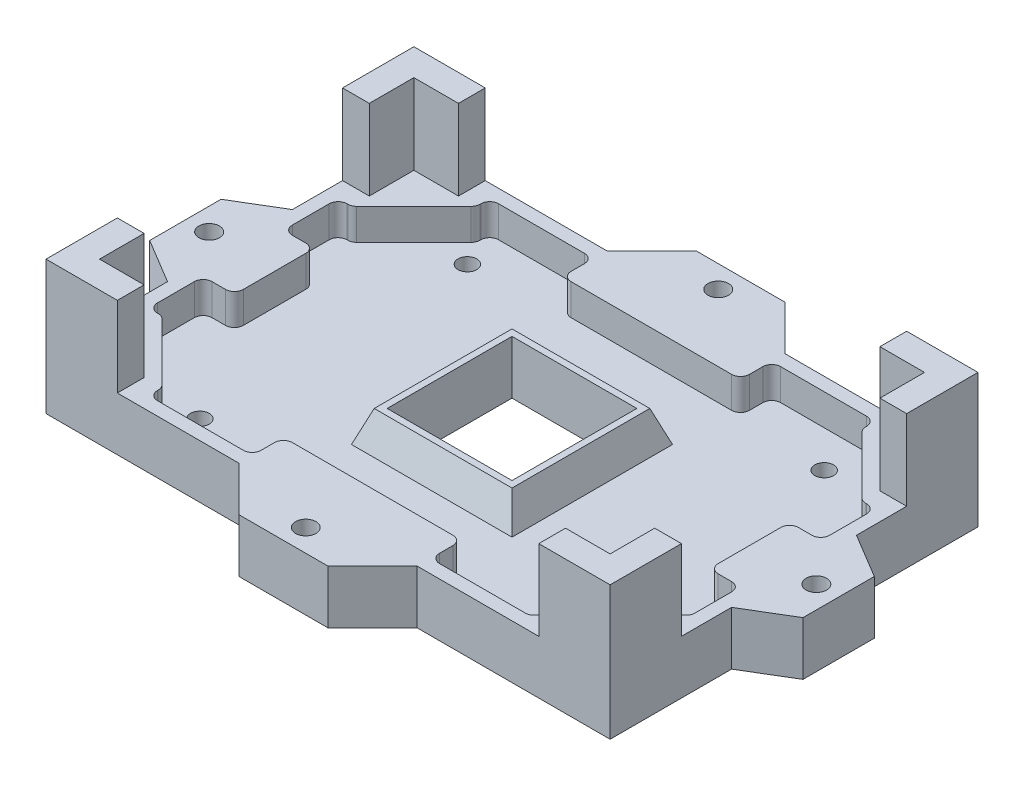
SolidWorks part; units mm, degrees
ref_plane "Спереди" through (0, 0, 0) normal (0, 0, 1) x (1, 0, 0)
ref_plane "Сверху" through (0, 0, 0) normal (0, 1, 0) x (1, 0, 0)
ref_plane "Справа" through (0, 0, 0) normal (1, 0, 0) x (0, 0, -1)
ref_plane "Плоскость4" through (0, 77.196, 0) normal (0, 1, 0) x (1, 0, 0)
sketch "Эскиз1" plane through (0, 77.196, 0) normal (0, 1, 0) x (1, 0, 0)
  line L0 (50.809, -75.5231) -> (50.809, -103.5231)
  line L1 (50.809, -103.5231) -> (78.809, -103.5231)
  line L2 (78.809, -103.5231) -> (78.809, -75.5231)
  line L3 (78.809, -75.5231) -> (50.809, -75.5231)
  line L4 (1.559, -48.2731) -> (1.559, -130.7731)
  line L5 (1.559, -130.7731) -> (128.059, -130.7731)
  line L6 (128.059, -130.7731) -> (128.059, -48.2731)
  line L7 (128.059, -48.2731) -> (1.559, -48.2731)
  circle A0 centre (24.809, -59.5231) radius 2.1
  circle A1 centre (104.809, -59.5231) radius 2.1
  circle A2 centre (104.809, -119.5231) radius 2.1
  circle A3 centre (24.809, -119.5231) radius 2.1
extrude "Бобышка-Вытянуть1" add sketch "Эскиз1" along normal blind 5
ref_plane "Плоскость5" through (0, 82.196, 0) normal (0, 1, 0) x (1, 0, 0)
sketch "Эскиз2" plane through (0, 82.196, 0) normal (0, 1, 0) x (1, 0, 0)
  line L0 (46.809, -71.5231) -> (82.809, -71.5231)
  line L1 (46.809, -107.5231) -> (82.809, -107.5231)
  line L2 (78.809, -103.5231) -> (78.809, -75.5231)
  line L3 (78.809, -75.5231) -> (50.809, -75.5231)
  line L4 (82.809, -107.5231) -> (82.809, -71.5231)
  line L5 (46.809, -71.5231) -> (46.809, -107.5231)
  line L6 (50.809, -75.5231) -> (50.809, -103.5231) construction
  line L7 (78.809, -75.5231) -> (50.809, -75.5231) construction
  line L8 (50.809, -75.5231) -> (50.809, -103.5231)
  line L9 (50.809, -103.5231) -> (78.809, -103.5231)
  line L14 (1.559, -48.2731) -> (1.559, -68.2731)
  line L15 (1.559, -48.2731) -> (1.559, -130.7731) construction
  line L16 (1.559, -48.2731) -> (21.559, -48.2731)
  line L17 (128.059, -48.2731) -> (1.559, -48.2731) construction
  line L18 (21.559, -48.2731) -> (21.559, -54.2731)
  line L19 (1.559, -68.2731) -> (7.559, -68.2731)
  line L20 (7.559, -68.2731) -> (21.559, -54.2731)
  line L21 (1.559, -130.7731) -> (21.559, -130.7731)
  line L22 (1.559, -130.7731) -> (128.059, -130.7731) construction
  line L23 (21.559, -130.7731) -> (21.559, -124.7731)
  line L24 (1.559, -130.7731) -> (1.559, -110.7731)
  line L25 (1.559, -110.7731) -> (7.559, -110.7731)
  line L26 (7.559, -110.7731) -> (21.559, -124.7731)
  line L27 (128.059, -48.2731) -> (108.059, -48.2731)
  line L28 (128.059, -48.2731) -> (128.059, -68.2731)
  line L29 (128.059, -130.7731) -> (128.059, -48.2731) construction
  line L30 (108.059, -48.2731) -> (108.059, -54.2731)
  line L31 (128.059, -68.2731) -> (122.059, -68.2731)
  line L32 (122.059, -68.2731) -> (108.059, -54.2731)
  line L33 (128.059, -130.7731) -> (108.059, -130.7731)
  line L34 (-8.25, -130.7731) -> (8.25, -130.7731) construction
  line L35 (128.059, -130.7731) -> (128.059, -110.7731)
  line L36 (128.059, -110.7731) -> (122.059, -110.7731)
  line L37 (108.059, -130.7731) -> (108.059, -124.7731)
  line L38 (108.059, -124.7731) -> (122.059, -110.7731)
  line L39 (118.059, -80.5231) -> (128.059, -80.5231)
  line L40 (128.059, -80.5231) -> (128.059, -98.5231)
  line L41 (128.059, -98.5231) -> (118.059, -98.5231)
  line L42 (118.059, -98.5231) -> (118.059, -80.5231)
  line L45 (44.809, -48.2731) -> (44.809, -58.2731)
  line L46 (44.809, -58.2731) -> (84.809, -58.2731)
  line L47 (84.809, -58.2731) -> (84.809, -48.2731)
  line L48 (44.809, -48.2731) -> (84.809, -48.2731)
  line L49 (1.559, -80.5231) -> (1.559, -98.5231)
  line L50 (1.559, -98.5231) -> (11.559, -98.5231)
  line L51 (11.559, -98.5231) -> (11.559, -80.5231)
  line L52 (11.559, -80.5231) -> (1.559, -80.5231)
  line L53 (44.809, -130.7731) -> (84.809, -130.7731)
  line L54 (84.809, -130.7731) -> (84.809, -120.7731)
  line L55 (84.809, -120.7731) -> (44.809, -120.7731)
  line L56 (44.809, -130.7731) -> (44.809, -120.7731)
  line L57 (21.559, -48.2731) -> (21.559, -51.2731)
  line L58 (21.559, -51.2731) -> (44.809, -51.2731)
  line L59 (44.809, -51.2731) -> (44.809, -48.2731)
  line L60 (44.809, -48.2731) -> (21.559, -48.2731)
  line L61 (108.059, -48.2731) -> (108.059, -51.2731)
  line L62 (108.059, -51.2731) -> (84.809, -51.2731)
  line L63 (84.809, -51.2731) -> (84.809, -48.2731)
  line L64 (128.059, -68.2731) -> (125.059, -68.2731)
  line L65 (125.059, -68.2731) -> (125.059, -80.5231)
  line L66 (125.059, -80.5231) -> (128.059, -80.5231)
  line L67 (128.059, -80.5231) -> (128.059, -68.2731)
  line L68 (128.059, -110.7731) -> (125.059, -110.7731)
  line L69 (125.059, -110.7731) -> (125.059, -98.5231)
  line L70 (125.059, -98.5231) -> (128.059, -98.5231)
  line L71 (128.059, -110.7731) -> (128.059, -98.5231)
  line L72 (108.059, -130.7731) -> (108.059, -127.7731)
  line L73 (108.059, -127.7731) -> (84.809, -127.7731)
  line L74 (84.809, -127.7731) -> (84.809, -130.7731)
  line L75 (108.059, -130.7731) -> (84.809, -130.7731)
  line L76 (21.559, -130.7731) -> (21.559, -127.7731)
  line L77 (21.559, -127.7731) -> (44.809, -127.7731)
  line L78 (44.809, -127.7731) -> (44.809, -130.7731)
  line L79 (44.809, -130.7731) -> (21.559, -130.7731)
  line L80 (21.559, -130.7731) -> (21.559, -127.7731)
  line L81 (1.559, -68.2731) -> (4.559, -68.2731)
  line L82 (4.559, -68.2731) -> (4.559, -80.5231)
  line L83 (4.559, -80.5231) -> (1.559, -80.5231)
  line L84 (1.559, -68.2731) -> (1.559, -80.5231)
  line L85 (1.559, -110.7731) -> (4.559, -110.7731)
  line L86 (4.559, -110.7731) -> (4.559, -98.5231)
  line L87 (4.559, -98.5231) -> (1.559, -98.5231)
  line L88 (1.559, -98.5231) -> (1.559, -110.7731)
  line L89 (84.809, -48.2731) -> (108.059, -48.2731)
  line L90 (128.059, -80.5231) -> (128.059, -68.2731)
  line L91 (128.059, -110.7731) -> (128.059, -98.5231)
extrude "Бобышка-Вытянуть2" add sketch "Эскиз2" along normal blind 7 contours L19 L20 L18 L16 L14 | L45 L60 L18 L58 | L48 L45 L46 L47 | L89 L47 L62 L30 | L32 L31 L28 L27 L30 | L39 L67 L31 L65 | L42 L41 L40 L39 | L36 L71 L41 L69 | L38 L37 L33 L35 L36 | L75 L37 L73 L54 | L0 L5 L1 L4 L9 L8 L3 L2 | L56 L53 L54 L55 | L79 L56 L77 L23 | L26 L25 L24 L21 L23 | L50 L88 L25 L86 | L51 L52 L49 L50 | L19 L84 L52 L82 region at (64.809, 82.196, 72.0322) region at (9.8283, 82.196, 56.5424) region at (3.059, 82.196, 74.3981) region at (33.184, 82.196, 49.7731) region at (6.559, 82.196, 89.5231) region at (64.809, 82.196, 53.2731) region at (3.059, 82.196, 104.6481) region at (96.434, 82.196, 49.7731) region at (9.8283, 82.196, 122.5038) region at (119.7897, 82.196, 56.5424) region at (33.184, 82.196, 129.2731) region at (126.559, 82.196, 74.3981) region at (64.809, 82.196, 125.7731) region at (123.059, 82.196, 89.5231) region at (96.434, 82.196, 129.2731) region at (126.559, 82.196, 104.6481) region at (119.7897, 82.196, 122.5038)
chamfer "Фаска1" distance 7 angle 20 4 edges at (82.809, 89.196, 89.5231) (64.809, 89.196, 71.5231) (46.809, 89.196, 89.5231) (64.809, 89.196, 107.5231) first distance on face at (82.809, 85.696, 89.5231) first distance on face at (64.809, 85.696, 71.5231) first distance on face at (46.809, 85.696, 89.5231) first distance on face at (64.809, 85.696, 107.5231)
fillet "Скругление1" radius 2 32 edges at (44.809, 85.696, 120.7731) (44.809, 85.696, 127.7731) (21.559, 85.696, 124.7731) (21.559, 85.696, 127.7731) (7.559, 85.696, 110.7731) (4.559, 85.696, 110.7731) (11.559, 85.696, 98.5231) (4.559, 85.696, 98.5231) (11.559, 85.696, 80.5231) (4.559, 85.696, 80.5231) (4.559, 85.696, 68.2731) (84.809, 85.696, 120.7731) (84.809, 85.696, 127.7731) (108.059, 85.696, 127.7731) (108.059, 85.696, 124.7731) (122.059, 85.696, 110.7731) (125.059, 85.696, 110.7731) (125.059, 85.696, 98.5231) (118.059, 85.696, 98.5231) (118.059, 85.696, 80.5231) (125.059, 85.696, 80.5231) (125.059, 85.696, 68.2731) (122.059, 85.696, 68.2731) (108.059, 85.696, 54.2731) (108.059, 85.696, 51.2731) (84.809, 85.696, 51.2731) (84.809, 85.696, 58.2731) (44.809, 85.696, 51.2731) (21.559, 85.696, 51.2731) (44.809, 85.696, 58.2731) (7.559, 85.696, 68.2731) (21.559, 85.696, 54.2731)
ref_plane "Плоскость6" through (0, 89.196, 0) normal (0, 1, 0) x (1, 0, 0)
sketch "Эскиз3" plane through (0, 89.196, 0) normal (0, 1, 0) x (1, 0, 0)
  line L0 (1.559, -48.2731) -> (1.559, -64.2731)
  line L1 (1.559, -48.2731) -> (1.559, -130.7731) construction
  line L2 (1.559, -64.2731) -> (7.559, -64.2731)
  line L3 (1.559, -48.2731) -> (17.559, -48.2731)
  line L4 (1.559, -48.2731) -> (128.059, -48.2731) construction
  line L5 (17.559, -48.2731) -> (17.559, -54.2731)
  line L6 (17.559, -54.2731) -> (7.559, -54.2731)
  line L7 (7.559, -54.2731) -> (7.559, -64.2731)
  line L8 (1.559, -130.7731) -> (1.559, -114.7731)
  line L9 (-8.25, -130.7731) -> (8.25, -130.7731) construction
  line L10 (1.559, -114.7731) -> (7.559, -114.7731)
  line L11 (1.559, -130.7731) -> (17.559, -130.7731)
  line L12 (17.559, -130.7731) -> (17.559, -124.7731)
  line L13 (17.559, -124.7731) -> (7.559, -124.7731)
  line L14 (7.559, -124.7731) -> (7.559, -114.7731)
  line L15 (128.059, -48.2731) -> (128.059, -64.2731)
  line L16 (128.059, -48.2731) -> (128.059, -130.7731) construction
  line L17 (128.059, -64.2731) -> (122.059, -64.2731)
  line L18 (128.059, -48.2731) -> (112.059, -48.2731)
  line L19 (112.059, -48.2731) -> (112.059, -54.2731)
  line L20 (112.059, -54.2731) -> (122.059, -54.2731)
  line L21 (122.059, -54.2731) -> (122.059, -64.2731)
  line L22 (128.059, -130.7731) -> (128.059, -114.7731)
  line L23 (128.059, -114.7731) -> (122.059, -114.7731)
  line L24 (128.059, -130.7731) -> (112.059, -130.7731)
  line L26 (112.059, -130.7731) -> (112.059, -124.7731)
  line L27 (112.059, -124.7731) -> (122.059, -124.7731)
  line L28 (122.059, -124.7731) -> (122.059, -114.7731)
extrude "Бобышка-Вытянуть3" add sketch "Эскиз3" along normal blind 18
sketch "Эскиз4" plane through (0, 89.196, 0) normal (0, 1, 0) x (1, 0, 0)
  line L0 (-8.441, -81.5231) -> (-8.441, -97.5231)
  line L1 (1.559, -64.2731) -> (1.559, -114.7731) construction
  line L2 (1.559, -81.5231) -> (1.559, -75.5231)
  line L3 (-8.441, -81.5231) -> (1.559, -81.5231)
  line L4 (1.559, -81.5231) -> (1.559, -97.5231)
  line L5 (1.559, -97.5231) -> (-8.441, -97.5231)
  line L6 (1.559, -75.5231) -> (-8.441, -81.5231)
  line L7 (1.559, -97.5231) -> (1.559, -103.5231)
  line L8 (1.559, -103.5231) -> (-8.441, -97.5231)
  line L9 (128.059, -81.5231) -> (128.059, -97.5231)
  line L10 (128.059, -64.2731) -> (128.059, -114.7731) construction
  line L11 (128.059, -97.5231) -> (138.059, -97.5231)
  line L12 (138.059, -97.5231) -> (138.059, -81.5231)
  line L13 (138.059, -81.5231) -> (128.059, -81.5231)
  line L14 (128.059, -75.5231) -> (138.059, -81.5231)
  line L15 (128.059, -97.5231) -> (128.059, -103.5231)
  line L16 (128.059, -103.5231) -> (138.059, -97.5231)
  line L17 (128.059, -81.5231) -> (128.059, -75.5231)
  line L18 (54.809, -38.2731) -> (54.809, -48.2731)
  line L19 (54.809, -48.2731) -> (44.809, -48.2731)
  line L20 (17.559, -48.2731) -> (112.059, -48.2731) construction
  line L21 (74.809, -38.2731) -> (54.809, -38.2731)
  line L22 (54.809, -48.2731) -> (74.809, -48.2731)
  line L23 (74.809, -48.2731) -> (74.809, -38.2731)
  line L24 (74.809, -48.2731) -> (84.809, -48.2731)
  line L25 (84.809, -48.2731) -> (74.809, -38.2731)
  line L26 (44.809, -48.2731) -> (54.809, -38.2731)
  line L27 (74.809, -130.7731) -> (54.809, -130.7731)
  line L28 (-8.25, -130.7731) -> (8.25, -130.7731) construction
  line L29 (54.809, -130.7731) -> (44.809, -130.7731)
  line L30 (74.809, -130.7731) -> (84.809, -130.7731)
  line L31 (17.559, -130.7731) -> (112.059, -130.7731) construction
  line L32 (54.809, -130.7731) -> (54.809, -140.7731)
  line L33 (54.809, -140.7731) -> (74.809, -140.7731)
  line L34 (74.809, -140.7731) -> (74.809, -130.7731)
  line L35 (74.809, -140.7731) -> (84.809, -130.7731)
  line L36 (54.809, -140.7731) -> (44.809, -130.7731)
  circle A0 centre (64.809, -135.7731) radius 2.3
  circle A1 centre (-3.441, -89.1878) radius 2.3
  circle A2 centre (64.809, -43.2731) radius 2.3
  circle A3 centre (133.059, -89.5231) radius 2.3
extrude "Бобышка-Вытянуть4" add sketch "Эскиз4" against normal blind 12 contours L36 L32 L29 | L33 L34 L27 L32 A0 | L34 L35 L30 | L26 L19 L18 | L22 L23 L21 L18 A2 | L24 L25 L23 | L2 L6 L3 | L5 L4 L3 L0 A1 | L8 L7 L5 | L17 L13 L14 | L12 L13 L9 L11 A3 | L15 L16 L11 region at (-3.441, 89.196, 81.7118) region at (-1.7744, 89.196, 79.5231) region at (-1.7744, 89.196, 99.5231) region at (133.059, 89.196, 81.7118) region at (131.3923, 89.196, 79.5231) region at (131.3923, 89.196, 99.5231) region at (64.809, 89.196, 38.4967) region at (51.4756, 89.196, 44.9398) region at (78.1423, 89.196, 44.9398) region at (74.5854, 89.196, 135.7731) region at (78.1423, 89.196, 134.1065) region at (51.4756, 89.196, 134.1065)
